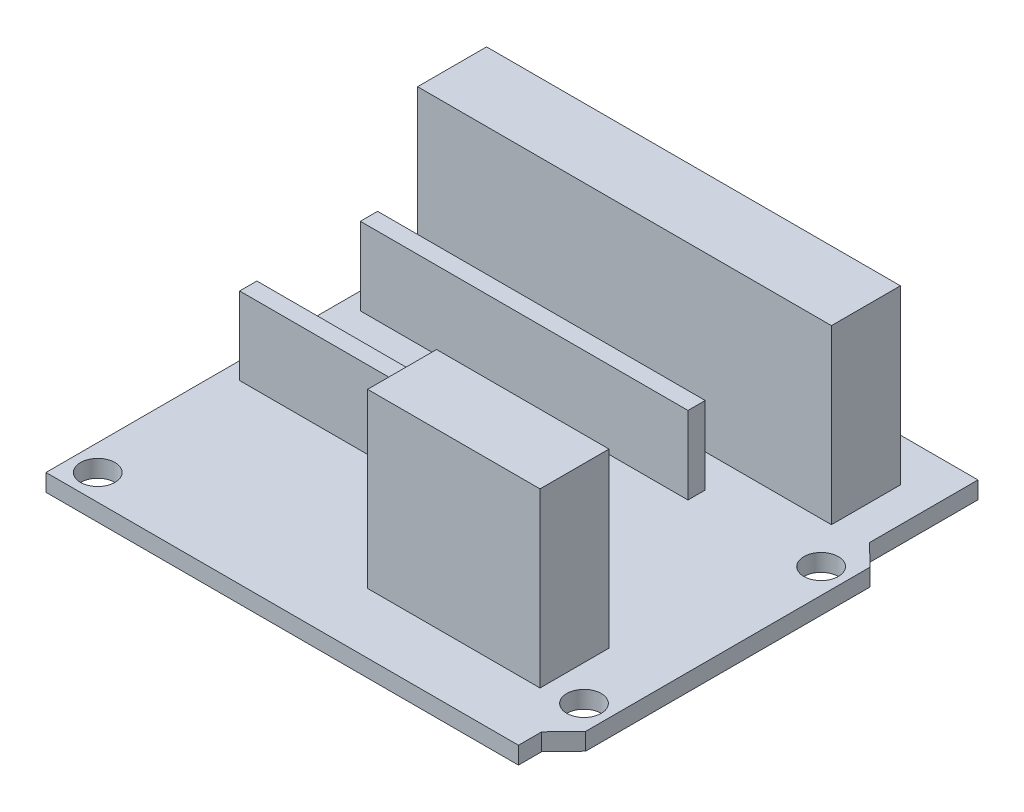
SolidWorks part; units mm, degrees
ref_plane "Front Plane" through (0, 0, 0) normal (0, 0, 1) x (1, 0, 0)
ref_plane "Top Plane" through (0, 0, 0) normal (0, 1, 0) x (1, 0, 0)
ref_plane "Right Plane" through (0, 0, 0) normal (1, 0, 0) x (0, 0, -1)
sketch "Sketch1" plane through (0, 0, 0) normal (0, 1, 0) x (1, 0, 0)
  line L0 (54.8, 53.3) -> (54.8, 40.7)
  line L1 (0, 0) -> (57.3, 0)
  line L2 (0, 0) -> (0, 53.3)
  line L3 (0, 53.3) -> (54.8, 53.3)
  line L4 (54.8, 40.7) -> (57.3, 38.3)
  line L5 (54.8, 0) -> (54.8, 2.6958)
  line L6 (0, 3) -> (3, 3) construction
  line L7 (3, 3) -> (3, 0) construction
  line L8 (54.8, 2.6958) -> (57.3, 5.3)
  line L9 (57.3, 5.3) -> (57.3, 0) construction
  line L10 (57.3, 38.3) -> (57.3, 5.3)
  line L11 (4, 53.3) -> (4, 50.8) construction
  line L12 (4, 50.8) -> (0, 50.8) construction
  line L13 (57.3, 8) -> (54.4, 8) construction
  line L14 (54.4, 8) -> (54.4, 10) construction
  line L15 (54.4, 8) -> (54.4, 0) construction
  line L16 (54.4, 35.5) -> (57.3, 35.5) construction
  line L17 (54.4, 35.5) -> (54.4, 53.3) construction
  circle A0 centre (3, 3) radius 2
  circle A1 centre (4, 50.8) radius 2
  circle A2 centre (54.4, 8) radius 2
  circle A3 centre (54.4, 35.5) radius 2
  point P19 (4, 50.8)
  point P20 (3, 3)
  point P30 (54.4, 35.5)
  point P31 (54.4, 8)
  dimension "D5" = 4
  dimension "D7" = 4
  dimension "D10" = 4
  dimension "D14" = 4
  dimension "D1" = 53.3
  dimension "D2" = 57.3
  dimension "D3" = 12.6
  dimension "D4" = 54.8
  dimension "D6" = 3
  dimension "D8" = 2.5
  dimension "D9" = 4
  dimension "D11" = 2.9
  dimension "D12" = 8
  dimension "D13" = 33
  dimension "D15" = 2.9
  dimension "D16" = 17.8
extrude "Boss-Extrude1" add sketch "Sketch1" along normal blind 2 contours L10 L4 L0 L3 L2 L1 L5 L8 A0 region at (28.2321, 0, -26.5425)
sketch "Sketch2" plane through (0, 2, 0) normal (0, 1, 0) x (1, 0, 0)
  line L0 (0, 34.4602) -> (2, 34.4602) construction
  line L1 (2, 36.4602) -> (40, 36.4602)
  line L2 (2, 36.4602) -> (2, 34.4602)
  line L3 (2, 34.4602) -> (40, 34.4602)
  line L4 (40, 36.4602) -> (40, 34.4602)
  line L5 (0, 0) -> (0, 53.3) construction
  dimension "D1" = 38
  dimension "D2" = 2
  dimension "D3" = 2
extrude "Boss-Extrude2" add sketch "Sketch2" along normal blind 9
pattern_linear "LPattern1" count 2 spacing 14 along (0, 0, 1) of "Boss-Extrude2"
sketch "Sketch3" plane through (0, 2, 0) normal (0, 1, 0) x (1, 0, 0)
  line L0 (57.3, 7) -> (50.3, 7) construction
  line L1 (57.3, 38.3) -> (57.3, 5.3) construction
  line L2 (50.3, 7) -> (50.3, 0) construction
  line L3 (0, 0) -> (54.8, 0) construction
  line L5 (50.3, 7) -> (30.3, 7)
  line L6 (50.3, 7) -> (50.3, 15)
  line L7 (50.3, 15) -> (30.3, 15)
  line L8 (30.3, 7) -> (30.3, 15)
  dimension "D1" = 7
  dimension "D2" = 7
  dimension "D3" = 20
  dimension "D4" = 8
extrude "Boss-Extrude3" add sketch "Sketch3" along normal blind 20
sketch "Sketch4" plane through (0, 2, 0) normal (0, 1, 0) x (1, 0, 0)
  line L0 (50.8, 53.3) -> (50.8, 48.3) construction
  line L1 (0, 53.3) -> (54.8, 53.3) construction
  line L2 (50.8, 48.3) -> (54.8, 48.3) construction
  line L3 (54.8, 53.3) -> (54.8, 40.7) construction
  line L5 (50.8, 48.3) -> (2.8, 48.3)
  line L6 (50.8, 48.3) -> (50.8, 40.3)
  line L7 (50.8, 40.3) -> (2.8, 40.3)
  line L8 (2.8, 48.3) -> (2.8, 40.3)
  dimension "D1" = 5
  dimension "D2" = 4
  dimension "D3" = 48
  dimension "D4" = 8
extrude "Boss-Extrude4" add sketch "Sketch4" along normal blind 20
sketch "Sketch6" plane through (0, 0, 0) normal (0, -1, 0) x (1, 0, 0)
  circle A0 centre (6.4883, -7.768) radius 0.5
  dimension "D1" = 1
extrude "Boss-Extrude6" add sketch "Sketch6" along normal blind 2.2
sketch "Sketch7" plane through (0, 0, 0) normal (0, -1, 0) x (1, 0, 0)
  line L0 (6.4883, -7.768) -> (11.8863, -9.8733)
pattern_linear "LPattern2" count 2 spacing 5 along (0.9317, 0, -0.3634) of "Boss-Extrude6"
